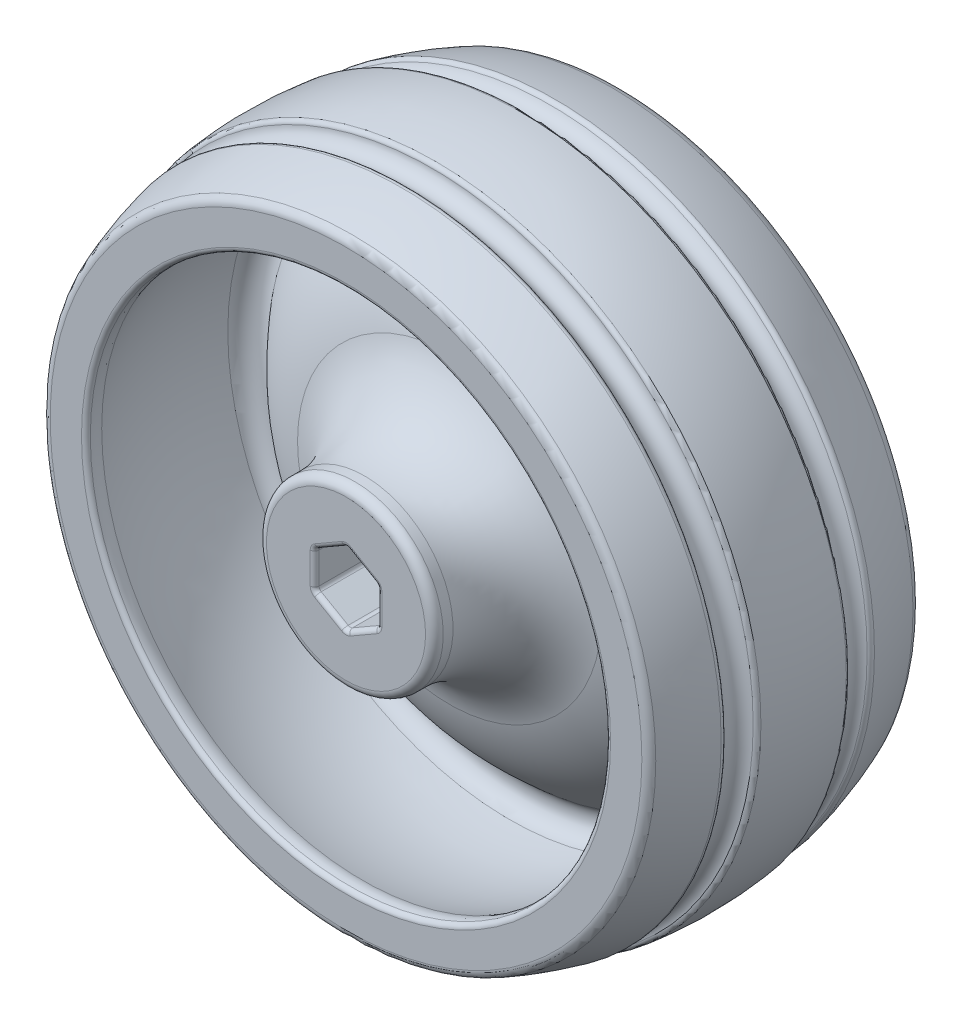
SolidWorks part; units mm, degrees
ref_plane "Front Plane" through (0, 0, 0) normal (0, 0, 1) x (1, 0, 0)
ref_plane "Top Plane" through (0, 0, 0) normal (0, 1, 0) x (1, 0, 0)
ref_plane "Right Plane" through (0, 0, 0) normal (1, 0, 0) x (0, 0, -1)
sketch "Sketch1" plane through (0, 0, 0) normal (0, 0, 1) x (1, 0, 0)
  line L5 (-2, -2) -> (2, 2) construction
  line L6 (-2, 2) -> (2, -2) construction
  line L7 (0, 4.1) -> (-3.5507, 2.05)
  line L8 (-3.5507, 2.05) -> (-3.5507, -2.05)
  line L9 (-3.5507, -2.05) -> (0, -4.1)
  line L10 (0, -4.1) -> (3.5507, -2.05)
  line L11 (3.5507, -2.05) -> (3.5507, 2.05)
  line L12 (3.5507, 2.05) -> (0, 4.1)
  circle A0 centre (0, 0) radius 4.1 construction
  circle A1 centre (0, 0) radius 10
  circle A2 centre (0, 0) radius 4.1 construction
  point P0 (0, 0)
  dimension "D3" = 8.2
  dimension "D1" = 20
extrude "Boss-Extrude1" add sketch "Sketch1" along normal blind 15
sketch "Sketch2" plane through (0, 0, 0) normal (0, 0, -1) x (-1, 0, 0)
  circle A1 centre (0, 0) radius 10
  circle A2 centre (0, 0) radius 10
  dimension "D1" = 0
sketch "Sketch3" plane through (0, 0, 0) normal (0, 1, 0) x (1, 0, 0)
  line L0 (0, 15) -> (0, -15)
  line L1 (0, -15) -> (-34.1565, -15) construction
  line L2 (-34.1565, -15) -> (-34.1565, 15) construction
  line L3 (-34.1565, 15) -> (0, 15) construction
  line L4 (0, 0) -> (2.9245, 0)
  line L5 (-10, -15) -> (10, -15) construction
  line L6 (-10, -15) -> (10, -15) construction
  line L8 (6, 0) -> (-10, 0)
  line L9 (-10, 0) -> (-10, -4.2529)
  line L10 (-10, 0) -> (-10, -15) construction
  line L11 (10, 0) -> (-10, 0) construction
  line L12 (-36.5, -6.7611) -> (-36.5, 6.7611) construction
  circle A0 centre (2.9245, 0) radius 40
  circle A1 centre (-31.839, -14.0625) radius 2.5
  circle A2 centre (2.9245, 0) radius 35
  circle A3 centre (-31.839, 14.0625) radius 2.5
  circle A4 centre (-29.9082, 3.3194) radius 2
  circle A5 centre (-36.5, -6.7611) radius 1.5
  circle A6 centre (-36.5, 6.7611) radius 1.5
  spline S0 degree 3 poles (-29.6198, 15.2138) (-27.6507, 11.418) (-22.0197, 4.9547) (-16.6358, -1.7049) (0, 2) knots 0 0 0 0 0.218516 1 1 1 1
  spline S1 degree 1 poles (-34.0581, 12.9112) (1.0869, -2.8804) knots 0 0 1 1 construction
  spline S2 degree 3 poles (-34.0581, 12.9112) (-33.9111, 12.6278) (-33.6056, 12.0495) (-33.0352, 11.0118) (-32.3528, 9.8455) (-31.5822, 8.6437) (-30.6072, 7.259) (-29.5708, 5.9919) (-28.7806, 5.0761) (-28.0561, 4.2321) (-27.2106, 3.2699) (-25.6297, 1.5873) (-22.9617, -0.7553) (-18.6366, -3.0523) (-14.3777, -4.0324) (-11.0814, -4.252) (-8.9404, -4.2601) (-6.4033, -4.1273) (-3.6462, -3.7892) (-1.0196, -3.3286) (0.3953, -3.0344) (1.0869, -2.8804) knots 0 0 0 0 0.015625 0.03125 0.0625 0.09375 0.125 0.1875 0.238623 0.269873 0.3125 0.375 0.5 0.625 0.75 0.797337 0.828587 0.875 0.9375 0.96875 1 1 1 1
  dimension "D1" = 80
  dimension "D6" = 4
  dimension "D9" = 3
  dimension "D2" = 30
  dimension "D3" = 36.5
  dimension "D7" = 2
  dimension "D4" = 5
  dimension "D5" = 5
revolve "Revolve1" add sketch "Sketch3" angle 360 about L0 region at (-19.7428, 0, -2.6019) region at (-29.2831, 0, -14.1788) region at (-31.5635, 0, -10.581) region at (-31.839, 0, -14.0625) region at (-31.839, 0, 14.0625) region at (-33.9673, 0, 0.6353) region at (-30.6903, 0, -5.9945)
fillet "Fillet1" radius 10 1 edges at (-10, 0, 4.2529)
sketch "Sketch4" plane through (0, 0, 0) normal (0, 0, 1) x (1, 0, 0)
  line L6 (3.5507, 2.05) -> (0, 4.1)
  line L7 (0, 4.1) -> (-3.5507, 2.05)
  line L8 (-3.5507, 2.05) -> (-3.5507, -2.05)
  line L9 (-3.5507, -2.05) -> (0, -4.1)
  line L10 (0, -4.1) -> (3.5507, -2.05)
  line L11 (3.5507, -2.05) -> (3.5507, 2.05)
  line L12 (3.5507, 2.05) -> (0, 4.1)
  line L13 (0, 4.1) -> (-3.5507, 2.05)
  line L14 (-3.5507, 2.05) -> (-3.5507, -2.05)
  line L15 (-3.5507, -2.05) -> (0, -4.1)
  line L16 (0, -4.1) -> (3.5507, -2.05)
  line L17 (3.5507, -2.05) -> (3.5507, 2.05)
  dimension "D1" = 0
extrude "Cut-Extrude1" cut sketch "Sketch4" against normal through all
fillet "Fillet2" radius 0.5 6 edges at (-3.5507, -2.05, 6.8877) (0, -4.1, 6.8877) (3.5507, -2.05, 6.8877) (3.5507, 2.05, 6.8877) (0, 4.1, 6.8877) (-3.5507, 2.05, 6.8877)
fillet "Fillet3" radius 0.5 24 edges at (-3.5155, 1.9456, -1.237) (-0.0728, 4.0173, -1.237) (3.4427, 2.0717, -1.237) (3.5155, -1.9456, -1.237) (0.0728, -4.0173, -1.237) (-3.4427, -2.0717, -1.237) (-3.4837, 2.0113, 15) (-1.7754, 3.075, 15) (0, 4.0226, 15) (1.7754, 3.075, 15) (3.4837, 2.0113, 15) (3.5507, 0, 15) (3.4837, -2.0113, 15) (1.7754, -3.075, 15) (0, -4.0226, 15) (-1.7754, -3.075, 15) (-3.4837, -2.0113, 15) (-3.5507, 0, 15)
fillet "Fillet4" radius 1 1 edges at (10, 0, 15)
fillet "Fillet5" radius 0.5 4 edges at (-36.2188, 0, -8.2345) (-36.7258, 0, -5.2782) (-36.7258, 0, 5.2782) (-36.2188, 0, 8.2345)
sketch "Sketch5" plane through (0, 0, 15) normal (0, 0, 1) x (1, 0, 0)
  circle A0 centre (0, 0) radius 36.8345
extrude "Cut-Extrude2" cut sketch "Sketch5" along normal blind 10
fillet "Fillet6" radius 1 1 edges at (34.1565, 0, 15)
fillet "Fillet7" radius 0.56 1 edges at (-29.5214, 0, 15)
